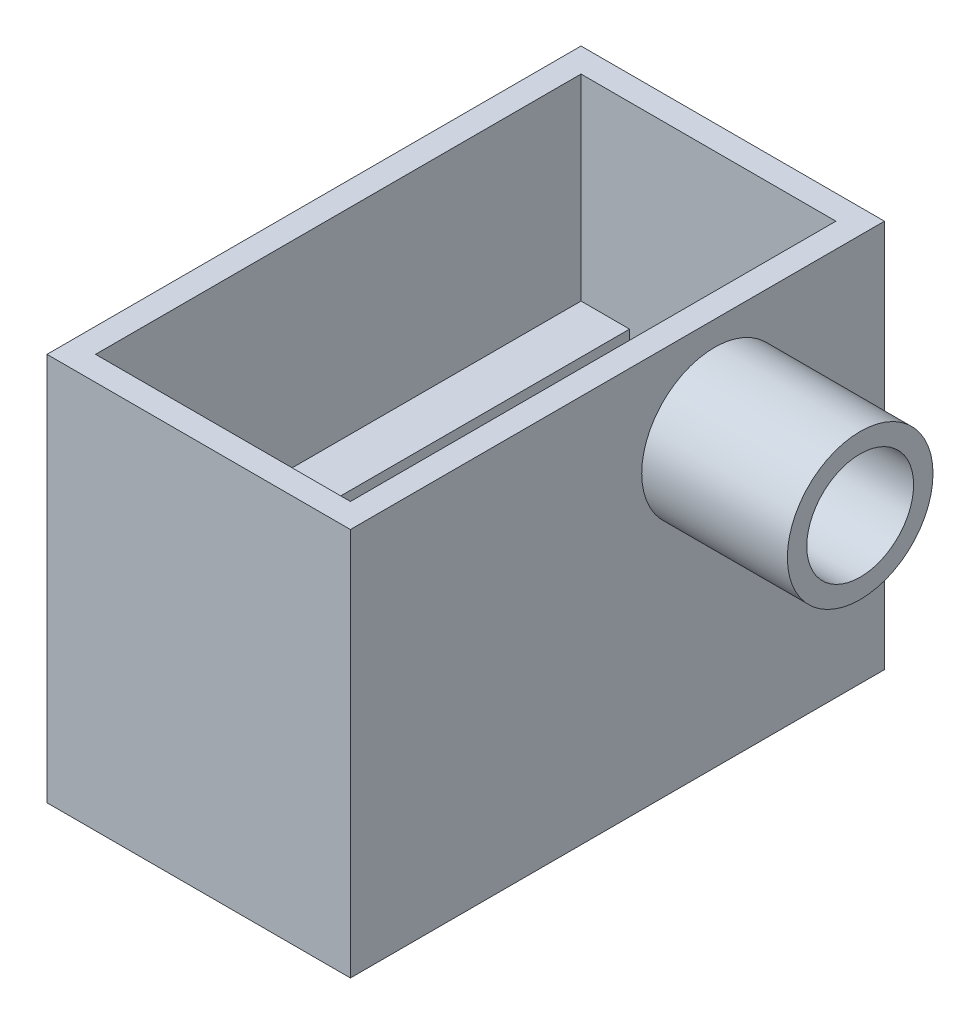
SolidWorks part; units mm, degrees
note: '?' marks a value the reader was unsure of. The reader was unsure of these and kept them because the rebuilt part matched: shared geometry of "Sketch2<3>", "Sketch6<3>".
ref_plane "Front Plane" through (0, 0, 0) normal (0, 0, 1) x (1, 0, 0)
ref_plane "Top Plane" through (0, 0, 0) normal (0, 1, 0) x (1, 0, 0)
ref_plane "Right Plane" through (0, 0, 0) normal (1, 0, 0) x (0, 0, -1)
sketch "Sketch1" plane through (0, 0, 0) normal (0, 1, 0) x (1, 0, 0)
  line L1 (-31.25, -55) -> (31.25, -55)
  line L2 (-31.25, -55) -> (-31.25, 55)
  line L3 (-31.25, 55) -> (31.25, 55)
  line L4 (31.25, -55) -> (31.25, 55)
  line L5 (-31.25, -55) -> (31.25, 55) construction
  line L6 (-31.25, 55) -> (31.25, -55) construction
  point P0 (0, 0)
  dimension "D1" = 62.5
  dimension "D2" = 110
extrude "Boss-Extrude1" add sketch "Sketch1" along normal blind 80
shell "Shell1" thickness 5
sketch "Sketch2" plane through (31.25, 0, 0) normal (1, 0, 0) x (0, 0, -1)
  line L0 (20, 80) -> (20, 0) construction
  line L1 (-55, 80) -> (55, 80) construction
  line L2 (55, 80) -> (55, 0) construction
  circle A0 centre (20, 60) radius 15
  circle A1 centre (20, 60) radius 11
  dimension "D2" = 30
  dimension "D3" = 22
  dimension "D1" = 20
  dimension "D4" = 35
extrude "Boss-Extrude2" add sketch "Sketch2" along normal blind 30
extrude "Cut-Extrude2" cut sketch "Sketch2<3>" against normal up to next contours L0 A1 | A1 L0
sketch "Sketch2<3>" plane through (31.25, 0, 0) normal (1, 0, 0) x (0, 0, -1) same geometry as "Sketch2"
sketch3d "3DSketch1"
  line L0 (26.25, 80, -50) -> (26.25, 11, -50) construction
  line L1 (26.25, 39.5, -50) -> (26.25, 34.5, -50)
  line L2 (26.25, 39.5, -50) -> (26.25, 39.5, 50)
  line L3 (26.25, 39.5, 50) -> (26.25, 34.5, 50)
  line L4 (26.25, 34.5, -50) -> (26.25, 34.5, 50)
  line L5 (26.25, 80, 50) -> (26.25, 11, 50) construction
  circle A0 centre (26.25, 60, -20) radius 11 construction
  point P10 (37.25, 60, -20)
  dimension "D1" = 5
  dimension "D2" = 20.5
extrude "Boss-Extrude3" add sketch "3DSketch1" along direction (-1, 0, 0) on the side of the normal blind 10 from surface at -52.5
sketch "Sketch5" [suppressed] plane through (0, 80, 0) normal (0, 1, 0) x (1, 0, 0)
  line L0 (40, -3.0529) -> (-40, -3.0529)
  line L1 (40, -25) -> (40, 25) construction
  line L2 (-40, 25) -> (-40, -25) construction
  line L3 (-12.9064, 25) -> (-12.9064, -25)
  line L4 (40, 25) -> (-40, 25) construction
  line L5 (-40, -25) -> (40, -25) construction
  circle A0 centre (-12.9064, -3.0529) radius 9.5
  dimension "D1" = 19
sketch "Sketch6" plane through (0, 11, 0) normal (0, 1, 0) x (1, 0, 0)
  line L0 (-26.25, -1) -> (26.25, -1) construction
  line L1 (-26.25, 50) -> (-26.25, -50) construction
  line L2 (26.25, -50) -> (26.25, 50) construction
  line L3 (2.75, -50) -> (2.75, 50) construction
  line L4 (-26.25, -50) -> (26.25, -50) construction
  line L5 (26.25, 50) -> (-26.25, 50) construction
  circle A0 centre (2.75, -1) radius 16.002
  circle A1 centre (2.75, -1) radius 14.5
  dimension "D3" = 32.004
  dimension "D4" = 29
  dimension "D1" = 29
  dimension "D2" = 51
extrude "Cut-Extrude4" cut sketch "Sketch6" against normal up to next contours A1
extrude "Cut-Extrude5" cut sketch "Sketch6<3>" against normal blind 8
sketch "Sketch6<3>" plane through (0, 11, 0) normal (0, 1, 0) x (1, 0, 0) same geometry as "Sketch6"
ref_axis "Axis2" through (2.75, 0, 1) along (0, 1, 0)?
sketch "Sketch7" plane through (0, 11, 0) normal (0, 1, 0) x (1, 0, 0)
  circle A0 centre (2.75, -36) radius 4.7625
  circle A1 centre (2.75, -1) radius 16.002 construction
  circle A2 centre (2.75, 34) radius 4.7625
  dimension "D1" = 9.525
  dimension "D3" = 9.525
  dimension "D2" = 35
  dimension "D4" = 35
extrude "Cut-Extrude6" cut sketch "Sketch7" against normal through all
ref_axis "Axis3" through (2.75, 0, 36) along (0, 1, 0)?
ref_axis "Axis4" through (2.75, 0, -34) along (0, 1, 0)?
ref_axis "Axis5" through (61.25, 60, -20) along (-1, 0, 0)?
equation "\"7mmmm\"=2"
